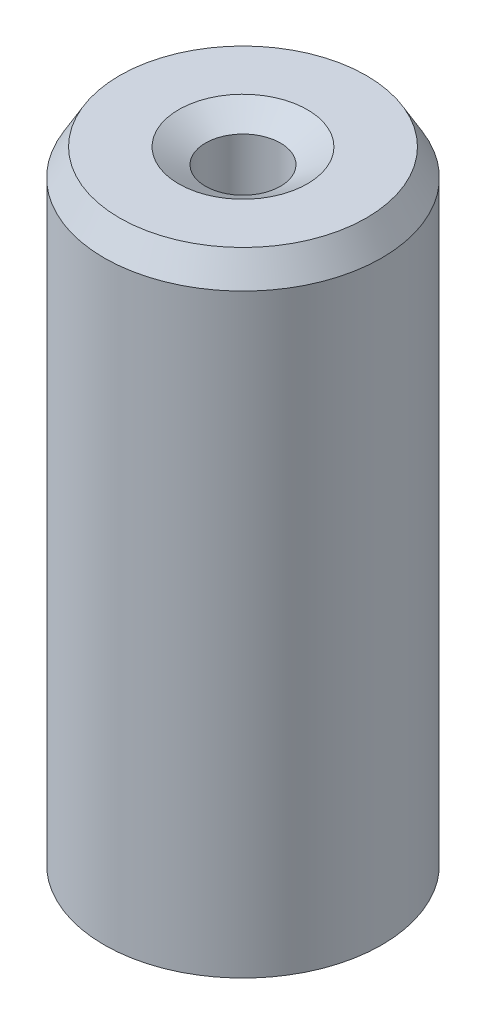
SolidWorks part; units mm, degrees
ref_plane "Front Plane" through (0, 0, 0) normal (0, 0, 1) x (1, 0, 0)
ref_plane "Top Plane" through (0, 0, 0) normal (0, 1, 0) x (1, 0, 0)
ref_plane "Right Plane" through (0, 0, 0) normal (1, 0, 0) x (0, 0, -1)
sketch "Sketch1" plane through (0, 0, 0) normal (0, 1, 0) x (1, 0, 0)
  circle A0 centre (0, 0) radius 5
  dimension "SLEEVE_OD" = 10
extrude "Boss-Extrude1" add sketch "Sketch1" along normal blind 22.9425
sketch "Sketch2" plane through (0, 0, 0) normal (0, 1, 0) x (1, 0, 0)
  circle A0 centre (0, 0) radius 1.3499
  dimension "BORE_D" = 2.6999
extrude "Cut-Extrude1" cut sketch "Sketch2" along normal through all
chamfer "Chamfer1" distance 0.9661 angle 30 4 edges at (0, 22.9425, 1.3499) (0, 0, 1.3499) (0, 0, 5) (0, 22.9425, 5) first distance on face at (0, 22.9425, 1.3499) first distance on face at (0, 0, 1.3499) first distance on face at (0, 22.9425, 5)
